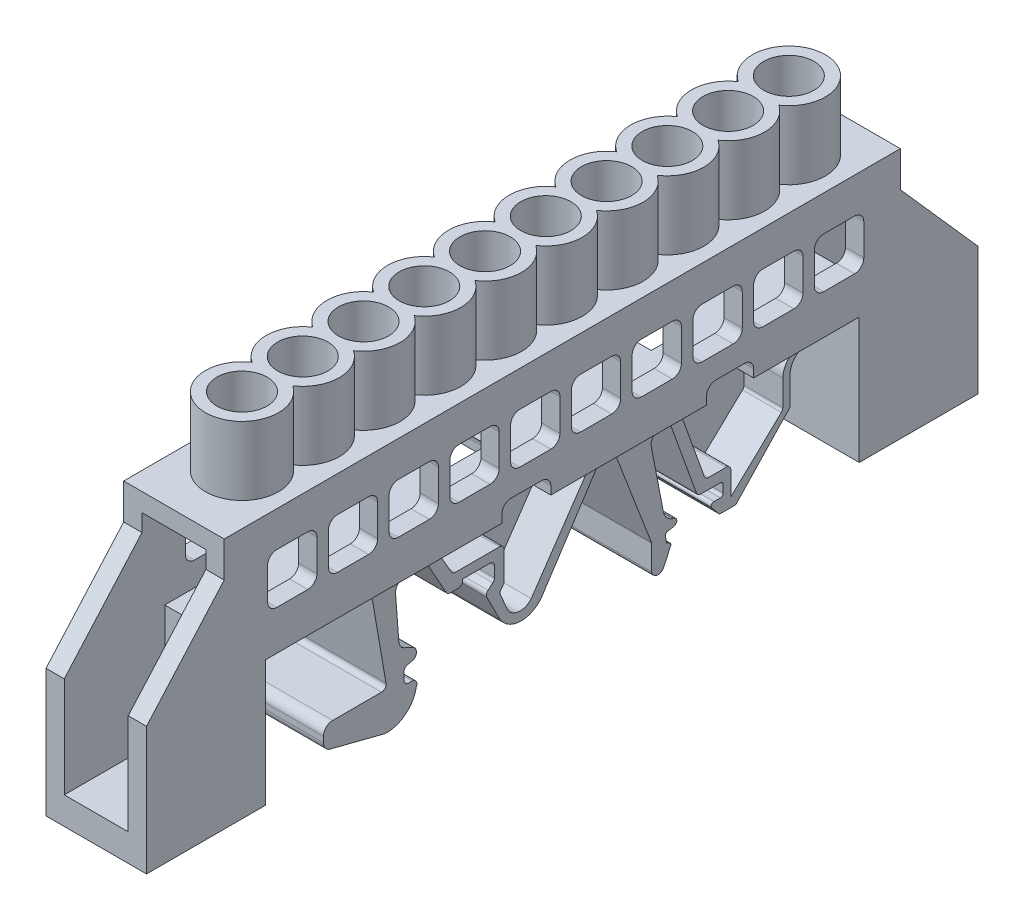
SolidWorks part; units mm, degrees
ref_plane "Plano frontal" through (0, 0, 0) normal (0, 0, 1) x (1, 0, 0)
ref_plane "Plano superior" through (0, 0, 0) normal (0, 1, 0) x (1, 0, 0)
ref_plane "Plano direito" through (0, 0, 0) normal (1, 0, 0) x (0, 0, -1)
sketch "Esboço3" plane through (0, 0, 0) normal (1, 0, 0) x (0, 0, -1)
  line L0 (0, 0) -> (91.0675, 0) construction
  line L1 (8.5, 27.5) -> (82.5, 27.5)
  line L2 (82.5, 27.5) -> (82.5, 23.613)
  line L3 (82.5, 23.613) -> (91, 14)
  line L4 (91, 14) -> (91, 0)
  line L5 (91, 0) -> (78, 0)
  line L6 (78, 0) -> (78, 13.7898)
  line L7 (78, 13.7898) -> (66.4493, 13.7898)
  line L8 (13, 13.7898) -> (13, 0)
  line L9 (13, 0) -> (0, 0)
  line L10 (0, 0) -> (0, 14)
  line L11 (0, 14) -> (8.5, 23.613)
  line L12 (8.5, 23.613) -> (8.5, 27.5)
  line L13 (25.2994, 22.613) -> (25.2994, 19.1387)
  line L14 (14.2493, 23.613) -> (17.6494, 23.613)
  line L15 (13.2493, 22.613) -> (13.2493, 19.1387)
  line L16 (14.2493, 18.1387) -> (17.6494, 18.1387)
  line L17 (18.6494, 22.613) -> (18.6494, 19.1387)
  line L18 (20.8993, 18.1387) -> (24.2994, 18.1387)
  line L19 (19.8993, 22.613) -> (19.8993, 19.1387)
  line L20 (20.8993, 23.613) -> (24.2994, 23.613)
  line L21 (31.9494, 22.613) -> (31.9494, 19.1387)
  line L22 (27.5493, 18.1387) -> (30.9494, 18.1387)
  line L23 (26.5493, 22.613) -> (26.5493, 19.1387)
  line L24 (27.5493, 23.613) -> (30.9494, 23.613)
  line L25 (38.5994, 22.613) -> (38.5994, 19.1387)
  line L26 (34.1993, 18.1387) -> (37.5994, 18.1387)
  line L27 (33.1993, 22.613) -> (33.1993, 19.1387)
  line L28 (34.1993, 23.613) -> (37.5994, 23.613)
  line L29 (45.2494, 22.613) -> (45.2494, 19.1387)
  line L30 (40.8493, 18.1387) -> (44.2494, 18.1387)
  line L31 (39.8493, 22.613) -> (39.8493, 19.1387)
  line L32 (40.8493, 23.613) -> (44.2494, 23.613)
  line L33 (51.8994, 22.613) -> (51.8994, 19.1387)
  line L34 (47.4993, 18.1387) -> (50.8994, 18.1387)
  line L35 (46.4993, 22.613) -> (46.4993, 19.1387)
  line L36 (47.4993, 23.613) -> (50.8994, 23.613)
  line L37 (58.5494, 22.613) -> (58.5494, 19.1387)
  line L38 (54.1493, 18.1387) -> (57.5494, 18.1387)
  line L39 (53.1493, 22.613) -> (53.1493, 19.1387)
  line L40 (54.1493, 23.613) -> (57.5494, 23.613)
  line L41 (65.1994, 22.613) -> (65.1994, 19.1387)
  line L42 (60.7993, 18.1387) -> (64.1994, 18.1387)
  line L43 (59.7993, 22.613) -> (59.7993, 19.1387)
  line L44 (60.7993, 23.613) -> (64.1994, 23.613)
  line L45 (71.8494, 22.613) -> (71.8494, 19.1387)
  line L46 (67.4493, 18.1387) -> (70.8494, 18.1387)
  line L47 (66.4493, 22.613) -> (66.4493, 19.1387)
  line L48 (67.4493, 23.613) -> (70.8494, 23.613)
  line L49 (78.4994, 22.613) -> (78.4994, 19.1387)
  line L50 (74.0993, 18.1387) -> (77.4994, 18.1387)
  line L51 (73.0993, 22.613) -> (73.0993, 19.1387)
  line L52 (74.0993, 23.613) -> (77.4994, 23.613)
  line L53 (24.8986, 13.7898) -> (26.4654, 4.7078)
  line L54 (25.9727, 4.1228) -> (20.6136, 4.1228)
  line L55 (19.6136, 3.1228) -> (19.6136, 2.5044)
  line L56 (20.3648, 1.5358) -> (26.3433, 0)
  line L57 (29.3216, 3.5007) -> (28.9168, 3.5007)
  line L58 (28.4168, 4.0007) -> (28.4168, 4.8015)
  line L59 (28.802, 5.2881) -> (29.39, 5.4269)
  line L60 (29.7752, 5.9135) -> (29.7752, 6.1301)
  line L61 (29.4959, 6.5788) -> (28.4198, 7.1079)
  line L62 (27.8639, 7.9307) -> (27.5063, 12.7153)
  line L63 (30.9494, 13.7898) -> (33.0561, 10.026)
  line L64 (33.4924, 9.7702) -> (34.3589, 9.7702)
  line L65 (34.8589, 10.2702) -> (34.8589, 10.4092)
  line L66 (34.8589, 10.4092) -> (37.8277, 10.4092)
  line L67 (38.3277, 9.9092) -> (38.3277, 8.7846)
  line L68 (38.1512, 8.4033) -> (37.6237, 7.9558)
  line L69 (37.5006, 7.3496) -> (38.8738, 4.6228)
  line L70 (43.4496, 4.309) -> (49.6431, 13.7898)
  line L71 (32.4008, 13.7898) -> (33.6215, 11.6938)
  line L72 (34.0536, 11.4455) -> (38.8914, 11.4455)
  line L73 (39.3914, 10.9455) -> (39.3914, 7.947)
  line L74 (39.2867, 7.6407) -> (39.0539, 7.3404)
  line L75 (38.9894, 6.8375) -> (39.7224, 5.1235)
  line L76 (42.3561, 4.8015) -> (48.4858, 13.7898)
  line L77 (51.578, 13.7898) -> (55.5089, 3.544)
  line L78 (55.5255, 3.4544) -> (55.5255, 0.7507)
  line L79 (56.8109, 0.4347) -> (57.6137, 2.1678)
  line L80 (57.4919, 2.4997) -> (57.2752, 2.6001)
  line L81 (57.1327, 2.7922) -> (57.0453, 3.4151)
  line L82 (57.2435, 3.6949) -> (58.0522, 3.858)
  line L83 (56.8109, 5.8254) -> (55.5255, 12.4711)
  line L84 (57.5494, 13.7898) -> (60.4373, 5.7577)
  line L85 (60.9079, 5.4269) -> (63.0498, 5.4269)
  line L86 (63.3498, 5.1269) -> (63.3498, 4.3007)
  line L87 (63.0498, 4.0007) -> (62.3518, 4.0007)
  line L88 (62.1197, 3.5107) -> (62.8575, 2.6096)
  line L89 (63.0896, 2.4997) -> (64.6062, 2.4997)
  line L90 (64.8242, 2.5935) -> (70.598, 8.6979)
  line L91 (70.6801, 8.904) -> (70.6801, 11.9455)
  line L92 (58.8279, 13.7898) -> (61.2954, 6.91)
  line L93 (61.7661, 6.5788) -> (63.6994, 6.5788)
  line L94 (64.1994, 6.0788) -> (64.1994, 3.5107)
  line L95 (64.1994, 3.5107) -> (69.73, 8.7561)
  line L96 (69.8859, 9.1189) -> (69.8859, 11.9455)
  line L97 (38.8914, 13.7898) -> (38.8914, 14.669)
  line L98 (39.8914, 15.669) -> (43.2494, 15.669)
  line L99 (44.2494, 14.669) -> (44.2494, 13.7898)
  line L100 (61.2954, 13.7898) -> (61.2954, 14.669)
  line L101 (62.2954, 15.669) -> (65.4493, 15.669)
  line L102 (66.4493, 14.669) -> (66.4493, 13.7898)
  line L103 (38.8914, 13.7898) -> (28.5035, 13.7898)
  line L104 (61.2954, 13.7898) -> (44.2494, 13.7898)
  line L105 (13, 13.7898) -> (24.8986, 13.7898)
  line L106 (28.5035, 13.7898) -> (24.8986, 13.7898)
  arc A0 (13.2493, 19.1387) -> (14.2493, 18.1387) centre (14.2493, 19.1387) ccw
  arc A1 (14.2493, 23.613) -> (13.2493, 22.613) centre (14.2493, 22.613) ccw
  arc A2 (17.6494, 23.613) -> (18.6494, 22.613) centre (17.6494, 22.613) cw
  arc A3 (17.6494, 18.1387) -> (18.6494, 19.1387) centre (17.6494, 19.1387) ccw
  arc A4 (24.2994, 18.1387) -> (25.2994, 19.1387) centre (24.2994, 19.1387) ccw
  arc A5 (19.8993, 19.1387) -> (20.8993, 18.1387) centre (20.8993, 19.1387) ccw
  arc A6 (20.8993, 23.613) -> (19.8993, 22.613) centre (20.8993, 22.613) ccw
  arc A7 (24.2994, 23.613) -> (25.2994, 22.613) centre (24.2994, 22.613) cw
  arc A8 (30.9494, 18.1387) -> (31.9494, 19.1387) centre (30.9494, 19.1387) ccw
  arc A9 (26.5493, 19.1387) -> (27.5493, 18.1387) centre (27.5493, 19.1387) ccw
  arc A10 (27.5493, 23.613) -> (26.5493, 22.613) centre (27.5493, 22.613) ccw
  arc A11 (30.9494, 23.613) -> (31.9494, 22.613) centre (30.9494, 22.613) cw
  arc A12 (37.5994, 18.1387) -> (38.5994, 19.1387) centre (37.5994, 19.1387) ccw
  arc A13 (33.1993, 19.1387) -> (34.1993, 18.1387) centre (34.1993, 19.1387) ccw
  arc A14 (34.1993, 23.613) -> (33.1993, 22.613) centre (34.1993, 22.613) ccw
  arc A15 (37.5994, 23.613) -> (38.5994, 22.613) centre (37.5994, 22.613) cw
  arc A16 (44.2494, 18.1387) -> (45.2494, 19.1387) centre (44.2494, 19.1387) ccw
  arc A17 (39.8493, 19.1387) -> (40.8493, 18.1387) centre (40.8493, 19.1387) ccw
  arc A18 (40.8493, 23.613) -> (39.8493, 22.613) centre (40.8493, 22.613) ccw
  arc A19 (44.2494, 23.613) -> (45.2494, 22.613) centre (44.2494, 22.613) cw
  arc A20 (50.8994, 18.1387) -> (51.8994, 19.1387) centre (50.8994, 19.1387) ccw
  arc A21 (46.4993, 19.1387) -> (47.4993, 18.1387) centre (47.4993, 19.1387) ccw
  arc A22 (47.4993, 23.613) -> (46.4993, 22.613) centre (47.4993, 22.613) ccw
  arc A23 (50.8994, 23.613) -> (51.8994, 22.613) centre (50.8994, 22.613) cw
  arc A24 (57.5494, 18.1387) -> (58.5494, 19.1387) centre (57.5494, 19.1387) ccw
  arc A25 (53.1493, 19.1387) -> (54.1493, 18.1387) centre (54.1493, 19.1387) ccw
  arc A26 (54.1493, 23.613) -> (53.1493, 22.613) centre (54.1493, 22.613) ccw
  arc A27 (57.5494, 23.613) -> (58.5494, 22.613) centre (57.5494, 22.613) cw
  arc A28 (64.1994, 18.1387) -> (65.1994, 19.1387) centre (64.1994, 19.1387) ccw
  arc A29 (59.7993, 19.1387) -> (60.7993, 18.1387) centre (60.7993, 19.1387) ccw
  arc A30 (60.7993, 23.613) -> (59.7993, 22.613) centre (60.7993, 22.613) ccw
  arc A31 (64.1994, 23.613) -> (65.1994, 22.613) centre (64.1994, 22.613) cw
  arc A32 (70.8494, 18.1387) -> (71.8494, 19.1387) centre (70.8494, 19.1387) ccw
  arc A33 (66.4493, 19.1387) -> (67.4493, 18.1387) centre (67.4493, 19.1387) ccw
  arc A34 (67.4493, 23.613) -> (66.4493, 22.613) centre (67.4493, 22.613) ccw
  arc A35 (70.8494, 23.613) -> (71.8494, 22.613) centre (70.8494, 22.613) cw
  arc A36 (77.4994, 18.1387) -> (78.4994, 19.1387) centre (77.4994, 19.1387) ccw
  arc A37 (73.0993, 19.1387) -> (74.0993, 18.1387) centre (74.0993, 19.1387) ccw
  arc A38 (74.0993, 23.613) -> (73.0993, 22.613) centre (74.0993, 22.613) ccw
  arc A39 (77.4994, 23.613) -> (78.4994, 22.613) centre (77.4994, 22.613) cw
  arc A40 (26.3433, 0) -> (29.7741, 2.709) centre (26.54, 3.2778) ccw
  arc A41 (29.7741, 2.709) -> (29.3216, 3.5007) centre (29.3169, 2.9729) ccw
  arc A42 (28.5035, 13.7898) -> (27.5063, 12.7153) centre (28.5035, 12.7898) ccw
  arc A43 (28.4198, 7.1079) -> (27.8639, 7.9307) centre (28.8611, 8.0053) cw
  arc A44 (19.6136, 2.5044) -> (20.3648, 1.5358) centre (20.6136, 2.5044) ccw
  arc A45 (20.6136, 4.1228) -> (19.6136, 3.1228) centre (20.6136, 3.1228) ccw
  arc A46 (29.7752, 6.1301) -> (29.4959, 6.5788) centre (29.2752, 6.1301) ccw
  arc A47 (29.39, 5.4269) -> (29.7752, 5.9135) centre (29.2752, 5.9135) ccw
  arc A48 (28.4168, 4.8015) -> (28.802, 5.2881) centre (28.9168, 4.8015) cw
  arc A49 (28.4168, 4.0007) -> (28.9168, 3.5007) centre (28.9168, 4.0007) ccw
  arc A50 (25.9727, 4.1228) -> (26.4654, 4.7078) centre (25.9727, 4.6228) ccw
  arc A51 (38.8738, 4.6228) -> (43.4496, 4.309) centre (41.2655, 5.9803) ccw
  arc A52 (33.0561, 10.026) -> (33.4924, 9.7702) centre (33.4924, 10.2702) ccw
  arc A53 (34.3589, 9.7702) -> (34.8589, 10.2702) centre (34.3589, 10.2702) ccw
  arc A54 (37.8277, 10.4092) -> (38.3277, 9.9092) centre (37.8277, 9.9092) cw
  arc A55 (38.3277, 8.7846) -> (38.1512, 8.4033) centre (37.8277, 8.7846) cw
  arc A56 (37.6237, 7.9558) -> (37.5006, 7.3496) centre (37.9472, 7.5745) ccw
  arc A57 (39.7224, 5.1235) -> (42.3561, 4.8015) centre (41.1447, 5.8254) ccw
  arc A58 (33.6215, 11.6938) -> (34.0536, 11.4455) centre (34.0536, 11.9455) ccw
  arc A59 (39.0539, 7.3404) -> (38.9894, 6.8375) centre (39.4491, 7.0341) ccw
  arc A60 (39.3914, 7.947) -> (39.2867, 7.6407) centre (38.8914, 7.947) cw
  arc A61 (38.8914, 11.4455) -> (39.3914, 10.9455) centre (38.8914, 10.9455) cw
  arc A62 (55.5255, 0.7507) -> (56.8109, 0.4347) centre (56.2238, 0.8191) ccw
  arc A63 (58.0522, 3.858) -> (57.898, 4.6228) centre (57.8887, 4.223) ccw
  arc A64 (57.898, 4.6228) -> (56.8109, 5.8254) centre (58.304, 6.0825) cw
  arc A65 (55.5255, 12.4711) -> (55.9933, 13.7898) centre (56.7096, 12.7935) cw
  arc A66 (55.5089, 3.544) -> (55.5255, 3.4544) centre (55.2755, 3.4544) cw
  arc A67 (57.6137, 2.1678) -> (57.4919, 2.4997) centre (57.3868, 2.2729) ccw
  arc A68 (57.2752, 2.6001) -> (57.1327, 2.7922) centre (57.3803, 2.8269) cw
  arc A69 (57.0453, 3.4151) -> (57.2435, 3.6949) centre (57.2929, 3.4499) cw
  arc A70 (70.6801, 11.9455) -> (72.1103, 13.7898) centre (72.7583, 11.8106) cw
  arc A71 (70.598, 8.6979) -> (70.6801, 8.904) centre (70.3801, 8.904) ccw
  arc A72 (64.6062, 2.4997) -> (64.8242, 2.5935) centre (64.6062, 2.7997) ccw
  arc A73 (62.8575, 2.6096) -> (63.0896, 2.4997) centre (63.0896, 2.7997) ccw
  arc A74 (62.3518, 4.0007) -> (62.1197, 3.5107) centre (62.3518, 3.7007) ccw
  arc A75 (63.3498, 4.3007) -> (63.0498, 4.0007) centre (63.0498, 4.3007) cw
  arc A76 (63.0498, 5.4269) -> (63.3498, 5.1269) centre (63.0498, 5.1269) cw
  arc A77 (69.8859, 11.9455) -> (70.8494, 13.7898) centre (72.3116, 11.8521) cw
  arc A78 (69.73, 8.7561) -> (69.8859, 9.1189) centre (69.3859, 9.1189) ccw
  arc A79 (63.6994, 6.5788) -> (64.1994, 6.0788) centre (63.6994, 6.0788) cw
  arc A80 (61.2954, 6.91) -> (61.7661, 6.5788) centre (61.7661, 7.0788) ccw
  arc A81 (60.4373, 5.7577) -> (60.9079, 5.4269) centre (60.9079, 5.9269) ccw
  arc A82 (43.2494, 15.669) -> (44.2494, 14.669) centre (43.2494, 14.669) cw
  arc A83 (38.8914, 14.669) -> (39.8914, 15.669) centre (39.8914, 14.669) cw
  arc A84 (61.2954, 14.669) -> (62.2954, 15.669) centre (62.2954, 14.669) cw
  arc A85 (65.4493, 15.669) -> (66.4493, 14.669) centre (65.4493, 14.669) cw
  dimension "D8" = 1
  dimension "D10" = 1
  dimension "D11" = 0.5
  dimension "D12" = 0.5
  dimension "D13" = 0.5
  dimension "D14" = 0.25
  dimension "D15" = 0.3
  dimension "D16" = 0.5
  dimension "D17" = 0.5
  dimension "D18" = 1
  dimension "D1" = 13
  dimension "D2" = 13
  dimension "D3" = 14
  dimension "D4" = 14
  dimension "D5" = 27.5
  dimension "D6" = 74
  dimension "D7" = 91
  dimension "D9" = 10
extrude "Ressalto-extrusão1" add sketch "Esboço3" along normal mid plane 11 contours L56 L0 A40 A41 L57 A49 L58 A48 L59 A47 L60 A46 L61 A43 L62 A42 L103 L97 A83 L98 A82 L99 L104 L100 A84 L101 A85 L102 L7 L6 L5 L4 L3 L2 L1 L12 L11 L10 L9 L8 L105 region at (0, 16.1423, -45.2921)
extrude "Ressalto-extrusão2" add sketch "Esboço3<3>" along normal mid plane 2 contours A83 L97 L103 L71 A58 L72 A61 L73 A60 L74 A59 L75 A57 L76 L104 L99 A82 L98 | A85 L101 A84 L100 L104 L92 A80 L93 A79 L94 L95 A78 L96 A77 L7 L102 region at (0, 10.6665, -64.7629) region at (0, 11.0331, -41.3113)
sketch "Esboço3<3>" plane through (0, 0, 0) normal (1, 0, 0) x (0, 0, -1) same geometry as "Esboço3"
extrude "Ressalto-extrusão3" add sketch "Esboço3<4>" along normal mid plane 10.5 contours L56 L0 A40 A41 L57 A49 L58 A48 L59 A47 L60 A46 L61 A43 L62 A42 L106 L53 A50 L54 A45 L55 A44 | A61 L72 A58 L71 L103 L63 A52 L64 A53 L65 L66 A54 L67 A55 L68 A56 L69 A51 L70 L104 L76 A57 L75 A59 L74 A60 L73 | L81 A69 L82 A63 A64 L83 A65 L104 L77 A66 L78 A62 L79 A67 L80 A68 | L84 A81 L85 A76 L86 A75 L87 A74 L88 A73 L89 A72 L90 A71 L91 A70 L7 A77 L96 A78 L95 L94 A79 L93 A80 L92 L104 region at (0, 0.9342, -23.3968) region at (0, 13.5751, -31.6751) region at (0, 13.1998, -70.967) region at (0, 7.9816, -55.0895)
sketch "Esboço3<4>" plane through (0, 0, 0) normal (1, 0, 0) x (0, 0, -1) same geometry as "Esboço3"
sketch "Esboço4" plane through (0, 0, 0) normal (0, 0, 1) x (1, 0, 0)
  line L0 (-5.5, 14) -> (-5.5, 23.613) construction
  line L1 (3.5, 3) -> (-3.5, 3)
  line L2 (3.5, 3) -> (3.5, 25.5)
  line L3 (3.5, 25.5) -> (-3.5, 25.5)
  line L4 (-3.5, 3) -> (-3.5, 25.5)
  line L6 (5.5, 14) -> (5.5, 23.613) construction
  line L7 (5.5, 0) -> (-5.5, 0) construction
  line L8 (5.5, 27.5) -> (-5.5, 27.5) construction
  dimension "D1" = 2
  dimension "D2" = 2
  dimension "D3" = 3
  dimension "D4" = 2
extrude "Corte-extrusão1" cut sketch "Esboço4" against normal blind 11
sketch "Esboço5" plane through (0, 0, -91) normal (0, 0, -1) x (-1, 0, 0)
  line L0 (-5.5, 23.613) -> (-5.5, 14) construction
  line L1 (-3.5, 3) -> (3.5, 3)
  line L2 (-3.5, 3) -> (-3.5, 25.5)
  line L3 (-3.5, 25.5) -> (3.5, 25.5)
  line L4 (3.5, 3) -> (3.5, 25.5)
  line L5 (-5.5, 27.5) -> (5.5, 27.5) construction
  line L6 (5.5, 23.613) -> (5.5, 14) construction
  line L7 (-5.5, 0) -> (5.5, 0) construction
  dimension "D1" = 2
  dimension "D2" = 2
  dimension "D3" = 2
  dimension "D4" = 3
extrude "Corte-extrusão2" cut sketch "Esboço5" against normal blind 11
sketch "Esboço6" plane through (0, 0, -80) normal (0, 0, -1) x (-1, 0, 0)
  line L0 (3.5, 14) -> (3.5, 23.613) construction
  line L1 (-3.5, 25.5) -> (3.5, 25.5)
  line L2 (-3.5, 25.5) -> (-3.5, 15.5)
  line L3 (-3.5, 15.5) -> (3.5, 15.5)
  line L4 (3.5, 25.5) -> (3.5, 15.5)
  dimension "D1" = 10
extrude "Corte-extrusão3" cut sketch "Esboço6" against normal blind 81
sketch "Esboço7" plane through (0, 27.5, 0) normal (0, 1, 0) x (1, 0, 0)
  line L0 (-4.5, 14.2493) -> (-4.5, 17.6494) construction
  line L1 (-3.5, 14.2493) -> (-5.5, 14.2493) construction
  line L2 (-3.5, 17.6494) -> (-5.5, 17.6494) construction
  line L3 (-4.5, 15.9494) -> (0, 15.9494) construction
  circle A0 centre (0, 15.9494) radius 2.75
  arc A1 (-2.2236, 19.2744) -> (2.2236, 19.2744) centre (0, 15.9494) ccw
  circle A2 centre (0, 22.5994) radius 2.75
  arc A3 (2.2236, 19.2744) -> (2.2236, 25.9244) centre (0, 22.5994) ccw
  circle A4 centre (0, 29.2494) radius 2.75
  arc A5 (2.2236, 25.9244) -> (2.2236, 32.5744) centre (0, 29.2494) ccw
  circle A6 centre (0, 35.8994) radius 2.75
  arc A7 (2.2236, 32.5744) -> (2.2236, 39.2244) centre (0, 35.8994) ccw
  circle A8 centre (0, 42.5494) radius 2.75
  arc A9 (2.2236, 39.2244) -> (2.2236, 45.8744) centre (0, 42.5494) ccw
  circle A10 centre (0, 49.1994) radius 2.75
  arc A11 (2.2236, 45.8744) -> (2.2236, 52.5244) centre (0, 49.1994) ccw
  circle A12 centre (0, 55.8494) radius 2.75
  arc A13 (2.2236, 52.5244) -> (2.2236, 59.1744) centre (0, 55.8494) ccw
  circle A14 centre (0, 62.4994) radius 2.75
  circle A16 centre (0, 69.1494) radius 2.75
  circle A18 centre (0, 75.7994) radius 2.75
  arc A19 (2.2236, 72.4744) -> (-2.2236, 72.4744) centre (0, 75.7994) ccw
  arc A20 (-2.2236, 25.9244) -> (-2.2236, 19.2744) centre (0, 22.5994) ccw
  arc A21 (-2.2236, 39.2244) -> (-2.2236, 32.5744) centre (0, 35.8994) ccw
  arc A22 (-2.2236, 32.5744) -> (-2.2236, 25.9244) centre (0, 29.2494) ccw
  arc A23 (-2.2236, 52.5244) -> (-2.2236, 45.8744) centre (0, 49.1994) ccw
  arc A24 (-2.2236, 45.8744) -> (-2.2236, 39.2244) centre (0, 42.5494) ccw
  arc A25 (-2.2236, 59.1744) -> (-2.2236, 52.5244) centre (0, 55.8494) ccw
  arc A26 (-2.2236, 65.8244) -> (-2.2236, 59.1744) centre (0, 62.4994) ccw
  arc A27 (-2.2236, 72.4744) -> (-2.2236, 65.8244) centre (0, 69.1494) ccw
  arc A28 (2.2236, 65.8244) -> (2.2236, 72.4744) centre (0, 69.1494) ccw
  arc A30 (2.2236, 59.1744) -> (2.2236, 65.8244) centre (0, 62.4994) ccw
  arc A31 (-0.5685, 58.54) -> (0.1104, 58.5009) centre (0, 62.4994) ccw [skipped]
  arc A32 (-0.5685, 65.19) -> (0.5685, 65.19) centre (0, 69.1494) ccw [skipped]
  dimension "D1" = 5.5
  dimension "D2" = 8
  dimension "D3" = 10
extrude "Ressalto-extrusão4" add sketch "Esboço7" along normal blind 7.5
sketch "Esboço8" plane through (0, 27.5, 0) normal (0, 1, 0) x (1, 0, 0)
  circle A0 centre (0, 15.9494) radius 2.75
  circle A1 centre (0, 22.5994) radius 2.75
  circle A2 centre (0, 29.2494) radius 2.75
  circle A3 centre (0, 35.8994) radius 2.75
  circle A4 centre (0, 42.5494) radius 2.75
  circle A5 centre (0, 49.1994) radius 2.75
  circle A6 centre (0, 55.8494) radius 2.75
  circle A7 centre (0, 62.4994) radius 2.75
  circle A8 centre (0, 69.1494) radius 2.75
  circle A9 centre (0, 75.7994) radius 2.75
  dimension "D1" = 10
extrude "Corte-extrusão4" cut sketch "Esboço8" against normal blind 3.5
